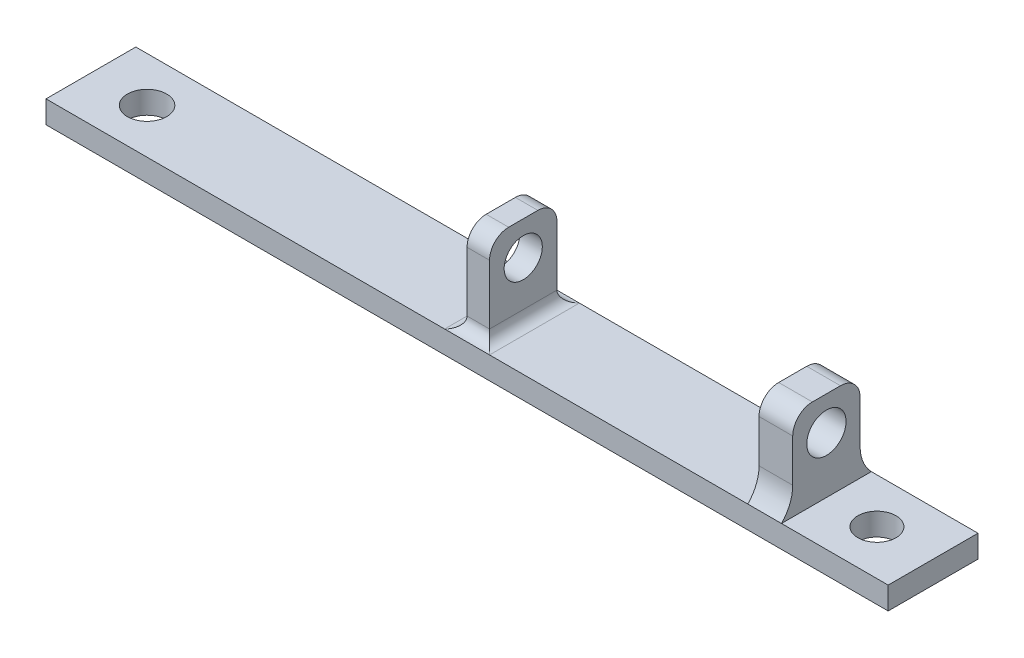
SolidWorks part; units mm, degrees
ref_plane "前视基准面" through (0, 0, 0) normal (0, 0, 1) x (1, 0, 0)
ref_plane "上视基准面" through (0, 0, 0) normal (0, 1, 0) x (1, 0, 0)
ref_plane "右视基准面" through (0, 0, 0) normal (1, 0, 0) x (0, 0, -1)
other "Configuration Table"
sketch "草图1" plane through (0, 0, 0) normal (0, 1, 0) x (1, 0, 0)
  line L0 (0, 0) -> (-32.5, 0) construction
  line L1 (-37.5, 4) -> (37.5, 4)
  line L2 (-37.5, 4) -> (-37.5, -4)
  line L3 (-37.5, -4) -> (37.5, -4)
  line L4 (37.5, 4) -> (37.5, -4)
  line L5 (-37.5, 4) -> (37.5, -4) construction
  line L6 (-37.5, -4) -> (37.5, 4) construction
  line L7 (-32.5, 0) -> (32.5, 0) construction
  circle A0 centre (-32.5, 0) radius 1.75
  circle A1 centre (32.5, 0) radius 1.7
  point P0 (0, 0)
  dimension "D5" = 3.5
  dimension "D6" = 3.4
  dimension "D1" = 8
  dimension "D2" = 75
  dimension "D3" = 32.5
  dimension "D4" = 65
extrude "凸台-拉伸1" add sketch "草图1" along normal blind 2
sketch "草图2" plane through (0, 0, 0) normal (1, 0, 0) x (0, 0, -1)
  line L0 (0, 0) -> (0, 2) construction
  line L1 (-4, 2) -> (4, 2) construction
  line L2 (0, 2) -> (0, 12) construction
  line L3 (0, 12) -> (0, 8) construction
  line L4 (0, 12) -> (0, 9) construction
  line L5 (0, 9) -> (0, 7) construction
  line L6 (0, 7) -> (0, 6) construction
  line L7 (0, 6) -> (0, 5) construction
  line L8 (0, 5) -> (0, 10) construction
  line L10 (-3, 10) -> (3, 10)
  line L11 (-3, 10) -> (-3, 2)
  line L12 (-3, 2) -> (3, 2)
  line L13 (3, 10) -> (3, 2)
  line L14 (-3, 10) -> (3, 2) construction
  line L15 (-3, 2) -> (3, 10) construction
  circle A0 centre (0, 7) radius 1.7
  dimension "D9" = 3.4
  dimension "D1" = 10
  dimension "D2" = 4
  dimension "D3" = 3
  dimension "D4" = 1
  dimension "D5" = 1
  dimension "D6" = 5
  dimension "D7" = 8
  dimension "D8" = 6
extrude "凸台-拉伸2" add sketch "草图2" along normal blind 1 and the other way blind 1
fillet "圆角2" radius 1 4 edges at (0, 2, -3) (1, 2, 0) (0, 2, 3) (-1, 2, 0)
fillet "圆角3" radius 1.7 2 edges at (0, 10, -3) (0, 10, 3)
ref_plane "基准面1" through (28, 0, 0) normal (1, 0, 0) x (0, 0, -1)
sketch "草图3" plane through (28, 0, 0) normal (1, 0, 0) x (0, 0, -1)
  line L0 (0, 10) -> (0, 2) construction
  line L1 (1.3, 10) -> (-1.3, 10) construction
  line L2 (4, 2) -> (-4, 2) construction
  line L3 (-1.7, 7) -> (1.7, 7) construction
  line L4 (-3, 2) -> (3, 2)
  line L5 (-3, 2) -> (-3, 10)
  line L6 (-3, 10) -> (3, 10)
  line L7 (3, 2) -> (3, 10)
  line L8 (-3, 2) -> (3, 10) construction
  line L9 (-3, 10) -> (3, 2) construction
  circle A0 centre (0, 7) radius 1.7 construction
  circle A1 centre (0, 7) radius 1.75
  point P6 (0, 6)
  dimension "D1" = 3.5
extrude "凸台-拉伸3" add sketch "草图3" against normal blind 3
fillet "圆角6" radius 1.75 2 edges at (26.5, 10, -3) (26.5, 10, 3)
fillet "圆角7" radius 3.5 2 edges at (26.5, 2, -3) (26.5, 2, 3)
